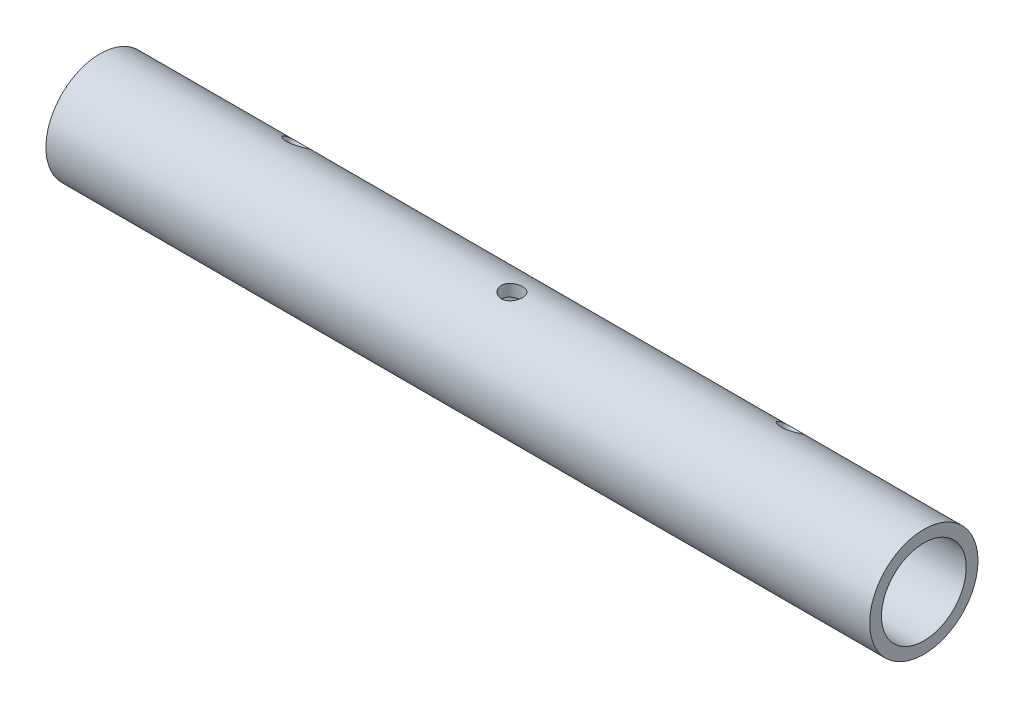
SolidWorks part; units mm, degrees
ref_plane "Front Plane" through (0, 0, 0) normal (0, 0, 1) x (1, 0, 0)
ref_plane "Top Plane" through (0, 0, 0) normal (0, 1, 0) x (1, 0, 0)
ref_plane "Right Plane" through (0, 0, 0) normal (1, 0, 0) x (0, 0, -1)
sketch "Sketch1" plane through (0, 0, 0) normal (1, 0, 0) x (0, 0, -1)
  circle A0 centre (0, 0) radius 16.7005
  circle A1 centre (0, 0) radius 13.0683
  dimension "D1" = 33.401
  dimension "D2" = 26.1366
extrude "Boss-Extrude1" add sketch "Sketch1" along normal blind 254
sketch "Sketch3" plane through (0, 0, 0) normal (0, 1, 0) x (1, 0, 0)
  line L0 (127, 16.7005) -> (127, -16.7005) construction
  line L1 (254, 16.7005) -> (0, 16.7005) construction
  line L2 (0, -16.7005) -> (254, -16.7005) construction
  circle A0 centre (127, 0) radius 3.2639
  dimension "D1" = 6.5278
extrude "Cut-Extrude2" cut sketch "Sketch3" against normal through all both and the other way through all
ref_axis "Axis1" through (254, 0, 0) along (-1, 0, 0)
ref_plane "Plane1" through (0, 0, 0) normal (0, 0.8192, -0.5736) x (-1, 0, 0)
sketch "Sketch4" plane through (0, 0, 0) normal (0, 0.8192, -0.5736) x (-1, 0, 0)
  line L0 (-254, 0) -> (-203.2, 0) construction
  line L1 (-254, 16.7005) -> (-254, -16.7005) construction
  line L2 (-254, 0) -> (0, 0) construction
  line L3 (0, 0) -> (-50.8, 0) construction
  circle A0 centre (-203.2, 0) radius 3.2639
  circle A1 centre (-50.8, 0) radius 3.2639
  dimension "D2" = 6.5278
  dimension "D1" = 50.8
extrude "Cut-Extrude3" cut sketch "Sketch4" against normal through all both and the other way through all
